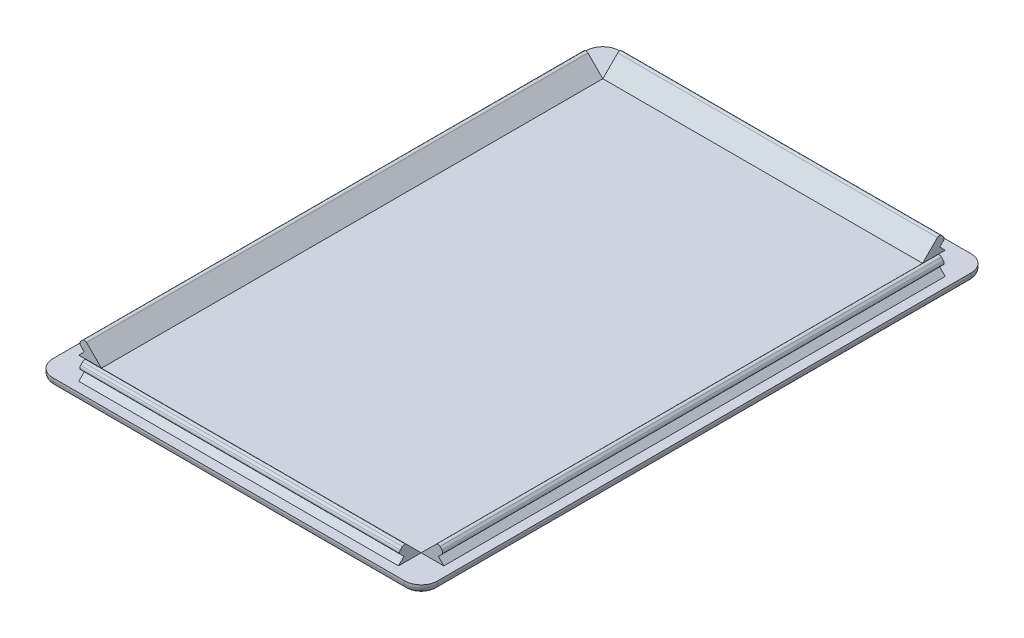
SolidWorks part; units mm, degrees
ref_plane "Front Plane" through (0, 0, 0) normal (0, 0, 1) x (1, 0, 0)
ref_plane "Top Plane" through (0, 0, 0) normal (0, 1, 0) x (1, 0, 0)
ref_plane "Right Plane" through (0, 0, 0) normal (1, 0, 0) x (0, 0, -1)
sketch "EDIT GLOBAL VARIABLE WITH PCB DIMENSIONS" plane through (0, 0, 0) normal (0, 1, 0) x (1, 0, 0)
  line L1 (-34.98, -51.49) -> (34.98, -51.49)
  line L2 (-34.98, -51.49) -> (-34.98, 51.49)
  line L3 (-34.98, 51.49) -> (34.98, 51.49)
  line L4 (34.98, -51.49) -> (34.98, 51.49)
  line L5 (-34.98, -51.49) -> (34.98, 51.49) construction
  line L6 (-34.98, 51.49) -> (34.98, -51.49) construction
  line L7 (-30.48, -46.99) -> (30.48, -46.99) construction
  line L8 (-30.48, -46.99) -> (-30.48, 46.99) construction
  line L9 (-30.48, 46.99) -> (30.48, 46.99) construction
  line L10 (30.48, -46.99) -> (30.48, 46.99) construction
  line L11 (-30.48, -46.99) -> (30.48, 46.99) construction
  line L12 (-30.48, 46.99) -> (30.48, -46.99) construction
  point P0 (0, 0)
  point P6 (0, 0)
  dimension "D3" = 4.5
  dimension "D4" = 4.5
  dimension "D2" = 93.98
  dimension "D17" = 60.96
extrude "Boss-Extrude1" add sketch "EDIT GLOBAL VARIABLE WITH PCB DIMENSIONS" along normal blind 1.5
fillet "Fillet1" radius 3 4 edges at (-34.98, 0.75, -51.49) (34.98, 0.75, -51.49) (34.98, 0.75, 51.49) (-34.98, 0.75, 51.49)
ref_plane "Plane1" through (-33.18, 0, 0) normal (-1, 0, 0) x (0, 0, 1)
ref_plane "Plane2" through (0, 0, 49.69) normal (0, 0, 1) x (1, 0, 0)
ref_plane "Plane3" through (33.18, 0, 0) normal (1, 0, 0) x (0, 0, -1)
ref_plane "Plane4" through (0, 0, -49.69) normal (0, 0, -1) x (-1, 0, 0)
ref_plane "Plane5" through (0, 0, -45.5687) normal (0, 0, -1) x (-1, 0, 0)
ref_plane "Plane6" through (-29.0587, 0, 0) normal (-1, 0, 0) x (0, 0, 1)
ref_plane "Plane7" through (0, 0, 45.5687) normal (0, 0, 1) x (1, 0, 0)
ref_plane "Plane8" through (29.0587, 0, 0) normal (1, 0, 0) x (0, 0, -1)
sketch "Sketch2" plane through (0, 0, 45.5687) normal (0, 0, 1) x (1, 0, 0)
  line L9 (33.18, 1.5) -> (29.0587, 1.5)
  line L11 (34.98, 1.5) -> (31.98, 1.5) construction
  line L12 (-31.98, 1.5) -> (31.98, 1.5) construction
  line L13 (29.0587, 1.5) -> (32.1193, 4.5607)
  line L14 (32.1193, 4.5607) -> (33.18, 3.5)
  line L15 (33.18, 3.5) -> (32.18, 2.5)
  line L16 (32.18, 2.5) -> (33.18, 1.5)
  line L17 (34.98, 1.5) -> (34.98, 0) construction
  line L18 (33.18, 3.5) -> (33.18, 1.5) construction
  dimension "D1" = 2
  dimension "D2" = 90
  dimension "D3" = 45
  dimension "D4" = 1.5
  dimension "D5" = 1.8
extrude "Boss-Extrude2" add sketch "Sketch2" against normal up to surface (91.1374 mm away) up to plane "Plane5"
sketch "Sketch3" plane through (0, 0, 45.5687) normal (0, 0, 1) x (1, 0, 0)
  line L9 (-33.18, 1.5) -> (-29.0587, 1.5)
  line L11 (-31.98, 1.5) -> (-34.98, 1.5) construction
  line L12 (-31.98, 1.5) -> (31.98, 1.5) construction
  line L13 (-29.0587, 1.5) -> (-32.1193, 4.5607)
  line L14 (-32.1193, 4.5607) -> (-33.18, 3.5)
  line L15 (-33.18, 3.5) -> (-32.18, 2.5)
  line L16 (-32.18, 2.5) -> (-33.18, 1.5)
  line L17 (-34.98, 0) -> (-34.98, 1.5) construction
  line L18 (-33.18, 3.5) -> (-33.18, 1.5) construction
  dimension "D1" = 45
  dimension "D2" = 90
  dimension "D3" = 1.5
  dimension "D4" = 2
  dimension "D5" = 1.8
extrude "Boss-Extrude3" add sketch "Sketch3" against normal up to surface (91.1374 mm away) up to plane "Plane5"
sketch "Sketch4" plane through (-29.0587, 0, 0) normal (-1, 0, 0) x (0, 0, 1)
  line L9 (-49.69, 1.5) -> (-45.5687, 1.5)
  line L12 (-48.49, 1.5) -> (-51.49, 1.5) construction
  line L13 (-48.49, 1.5) -> (48.49, 1.5) construction
  line L14 (-45.5687, 1.5) -> (-48.6293, 4.5607)
  line L15 (-48.6293, 4.5607) -> (-49.69, 3.5)
  line L16 (-49.69, 3.5) -> (-48.69, 2.5)
  line L17 (-48.69, 2.5) -> (-49.69, 1.5)
  line L18 (-51.49, 0) -> (-51.49, 1.5) construction
  dimension "D1" = 45
  dimension "D2" = 90
  dimension "D3" = 1.5
  dimension "D4" = 2
  dimension "D5" = 1.8
  dimension "D6" = 1.8
extrude "Boss-Extrude4" add sketch "Sketch4" against normal up to surface (58.1174 mm away) up to plane "Plane8"
sketch "Sketch5" plane through (-29.0587, 0, 0) normal (-1, 0, 0) x (0, 0, 1)
  line L0 (45.5687, 1.5) -> (49.69, 1.5)
  line L1 (-48.49, 1.5) -> (48.49, 1.5) construction
  line L2 (51.49, 1.5) -> (48.49, 1.5) construction
  line L3 (49.69, 1.5) -> (48.69, 2.5)
  line L4 (48.69, 2.5) -> (49.69, 3.5)
  line L5 (49.69, 3.5) -> (48.6293, 4.5607)
  line L6 (48.6293, 4.5607) -> (45.5687, 1.5)
  line L7 (51.49, 1.5) -> (51.49, 0) construction
  dimension "D1" = 45
  dimension "D2" = 90
  dimension "D3" = 1.5
  dimension "D4" = 90
  dimension "D5" = 1.8
  dimension "D6" = 1.8
  dimension "D7" = 2
extrude "Boss-Extrude5" add sketch "Sketch5" against normal up to surface (58.1174 mm away) up to plane "Plane8"
fillet "Fillet2" radius 0.5 8 edges at (0, 3.5, 49.69) (0, 4.5607, 48.6293) (-33.18, 3.5, 0) (-32.1193, 4.5607, 0) (0, 3.5, -49.69) (0, 4.5607, -48.6293) (33.18, 3.5, 0) (32.1193, 4.5607, 0)
fillet "Fillet3" radius 1 8 edges at (-34.1013, 0, -50.6113) (-34.98, 0, 0) (-34.1013, 0, 50.6113) (0, 0, 51.49) (34.1013, 0, 50.6113) (0, 0, -51.49) (34.1013, 0, -50.6113) (34.98, 0, 0)
equation "\"LENGTH\"= 3.7in  'longest of two dimensions of pcb"
equation "\"WIDTH\"= 2.4in   'shortest of two dimensions of pcb"
equation "\"D2@EDIT GLOBAL VARIABLE WITH PCB DIMENSIONS\" = \"LENGTH\""
equation "\"D17@EDIT GLOBAL VARIABLE WITH PCB DIMENSIONS\" = \"WIDTH\""
equation "\"HOLE_DIA\"= 0.1in  'mounting hole diameter"
equation "\"HOLE_DIST\"= 0.137795in  'distance to mount hole centerline from edge of PCB"
equation "\"HEIGHT\"= 0.944882in  'height of the enclosure"
